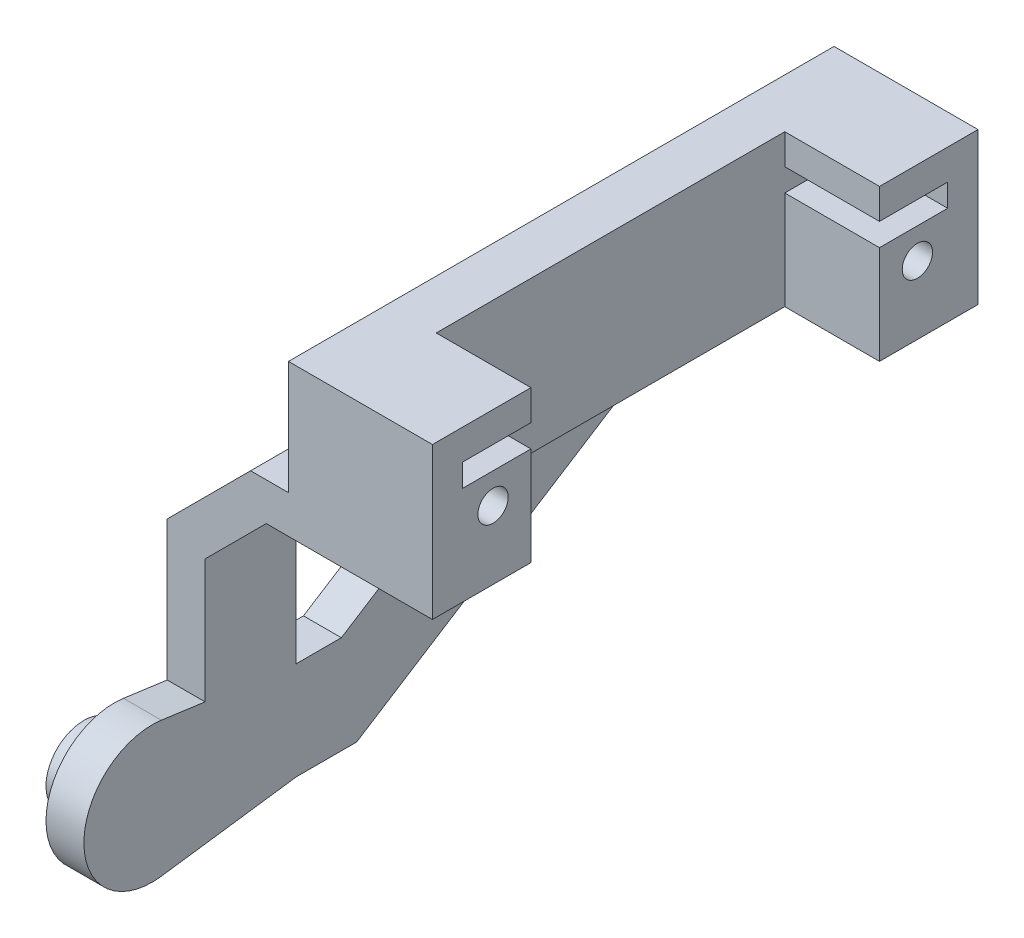
SolidWorks part; units mm, degrees
note: The reader was unsure of these and kept them because the rebuilt part matched: shared geometry of "草图6<3>".
ref_plane "前视基准面" through (0, 0, 0) normal (0, 0, 1) x (1, 0, 0)
ref_plane "上视基准面" through (0, 0, 0) normal (0, 1, 0) x (1, 0, 0)
ref_plane "右视基准面" through (0, 0, 0) normal (1, 0, 0) x (0, 0, -1)
sketch "草图1" plane through (0, 0, 0) normal (0, 0, 1) x (1, 0, 0)
  line L0 (0, 0) -> (0, 10)
  line L1 (0, 10) -> (-9.5, 10)
  line L2 (-9.5, 10) -> (-9.5, 2.5)
  line L3 (-9.5, 2.5) -> (-12, 2.5)
  line L4 (-17.5, -3) -> (-17.5, -19.5)
  line L5 (-17.5, -19.5) -> (-15, -19.5)
  line L6 (-15, -19.5) -> (-15, -4.0355)
  line L7 (-15, -4.0355) -> (-10.9645, 0)
  line L8 (-10.9645, 0) -> (0, 0)
  line L9 (-12, 2.5) -> (-17.5, -3)
  dimension "D1" = 10
  dimension "D2" = 9.5
  dimension "D4" = 2.5
  dimension "D5" = 2.5
  dimension "D3" = 2.5
  dimension "D6" = 29.5
  dimension "D7" = 8
  dimension "D8" = 45
  dimension "D9" = 2.5
extrude "凸台-拉伸1" add sketch "草图1" along normal mid plane 36
sketch "草图2" plane through (-17.5, 0, 0) normal (-1, 0, 0) x (0, 0, 1)
  line L0 (-1.5, -6.3649) -> (-1.5, -4.0355)
  line L1 (-1.5, -4.0355) -> (12, -4.0355)
  line L2 (12, -4.0355) -> (12, -13.0355)
  line L3 (9.0113, -13.0355) -> (-1.5, -6.3649)
  line L4 (-18, -3) -> (8, -19.5)
  line L5 (18, -19.5) -> (-18, -19.5) construction
  line L6 (8, -19.5) -> (-18, -19.5)
  line L7 (-18, -19.5) -> (-18, -3)
  line L9 (9.0113, -13.0355) -> (12, -13.0355)
  line L10 (18, -3) -> (18, -19.5) construction
  line L11 (18, -4.0355) -> (-18, -4.0355) construction
  dimension "D1" = 26
  dimension "D2" = 6
  dimension "D4" = 9
  dimension "D5" = 13.5
  dimension "D6" = 6
extrude "切除-拉伸1" cut sketch "草图2" against normal up to next
extrude "切除-拉伸2" cut sketch "草图3" against normal mid plane 12.5
sketch "草图3" plane through (0, 8.8945, 0.8332) normal (-1, 0, 0) x (0, -1, 0)
  line L9 (2.3945, 15.1668) -> (2.3945, 10.6668)
  line L10 (0.8945, 15.1668) -> (2.3945, 15.1668)
  line L11 (0.8945, 10.6668) -> (0.8945, 15.1668)
  line L12 (-3.1055, 10.6668) -> (0.8945, 10.6668)
  line L13 (0.8945, -12.3332) -> (-3.1055, -12.3332)
  line L14 (0.8945, -16.8332) -> (0.8945, -12.3332)
  line L15 (2.3945, -16.8332) -> (0.8945, -16.8332)
  line L16 (2.3945, -12.3332) -> (2.3945, -16.8332)
  line L17 (8.8945, -12.3332) -> (2.3945, -12.3332)
  line L22 (-3.1055, -12.3332) -> (-3.1055, 10.6668)
  line L23 (8.8945, -12.3332) -> (8.8945, 10.6668)
  line L24 (8.8945, 10.6668) -> (2.3945, 10.6668)
extrude "切除-拉伸3" cut sketch "草图4" along normal through all
sketch "草图4" plane through (0, 8.8945, 0.8332) normal (-1, 0, 0) x (0, -1, 0)
  circle A2 centre (4.3945, -14.8332) radius 1
  circle A3 centre (4.3945, 13.1668) radius 1
  circle A4 centre (4.3945, -14.8332) radius 2
  circle A5 centre (4.3945, 13.1668) radius 2
sketch "草图5" plane through (-9.5, 0, 0) normal (-1, 0, 0) x (0, 0, 1)
  circle A0 centre (14, 4.5) radius 2
  circle A1 centre (-14, 4.5) radius 2
  dimension "D1" = 4
  dimension "D2" = 4
extrude "切除-拉伸4" cut sketch "草图5" against normal blind 2
sketch "草图6" plane through (-15, 0, 0) normal (1, 0, 0) x (0, 0, -1)
  line L0 (-20.8864, -20.7257) -> (-10.0909, -19.2397) construction
  line L1 (-20.8864, -11.8098) -> (-12, -13.033) construction
  line L2 (-20.8864, -20.7257) -> (-10.0909, -19.2397)
  line L3 (-20.8864, -11.8098) -> (-12, -13.033)
  line L4 (-11.9816, -13.0355) -> (-10.0909, -13.2958) construction
  line L5 (-11.9816, -13.0355) -> (-10.0909, -13.2958)
  arc A0 (-10.0909, -19.2397) -> (-10.0909, -13.2958) centre (-10.5, -16.2678) ccw construction
  arc A1 (-20.8864, -11.8098) -> (-20.8864, -20.7257) centre (-21.5, -16.2678) ccw construction
  arc A2 (-10.0909, -19.2397) -> (-10.0909, -13.2958) centre (-10.5, -16.2678) ccw
  arc A3 (-20.8864, -11.8098) -> (-20.8864, -20.7257) centre (-21.5, -16.2678) ccw
  circle A4 centre (-21.5, -16.2678) radius 2.5
  line M1 (-18, -19.5) -> (-8, -19.5)
  line M9 (-18, -4.0355) -> (-18, -19.5)
  dimension "D1" = 5
extrude "凸台-拉伸3" add sketch "草图6" against normal up to surface (2.5 mm away) contours L3 A3 L2 A4 M1 M9 | A4 up to face at (-17.5, -8.1014, 6.0023)
extrude "凸台-拉伸4" add sketch "草图6<3>" against normal blind 2 from surface at -2.5 contours A4 starting at face at (-17.5, -12.8204, 12.124)
sketch "草图6<3>" plane through (-15, 0, 0) normal (1, 0, 0) x (0, 0, -1) same geometry as "草图6"
equation "\"D5@草图1\"= \"D4@草图1\""
equation "\"D9@草图1\"= \"D4@草图1\""
equation "\"0。5\"=0.721199"
equation "\"D2@草图5\"= \"D1@草图5\""
